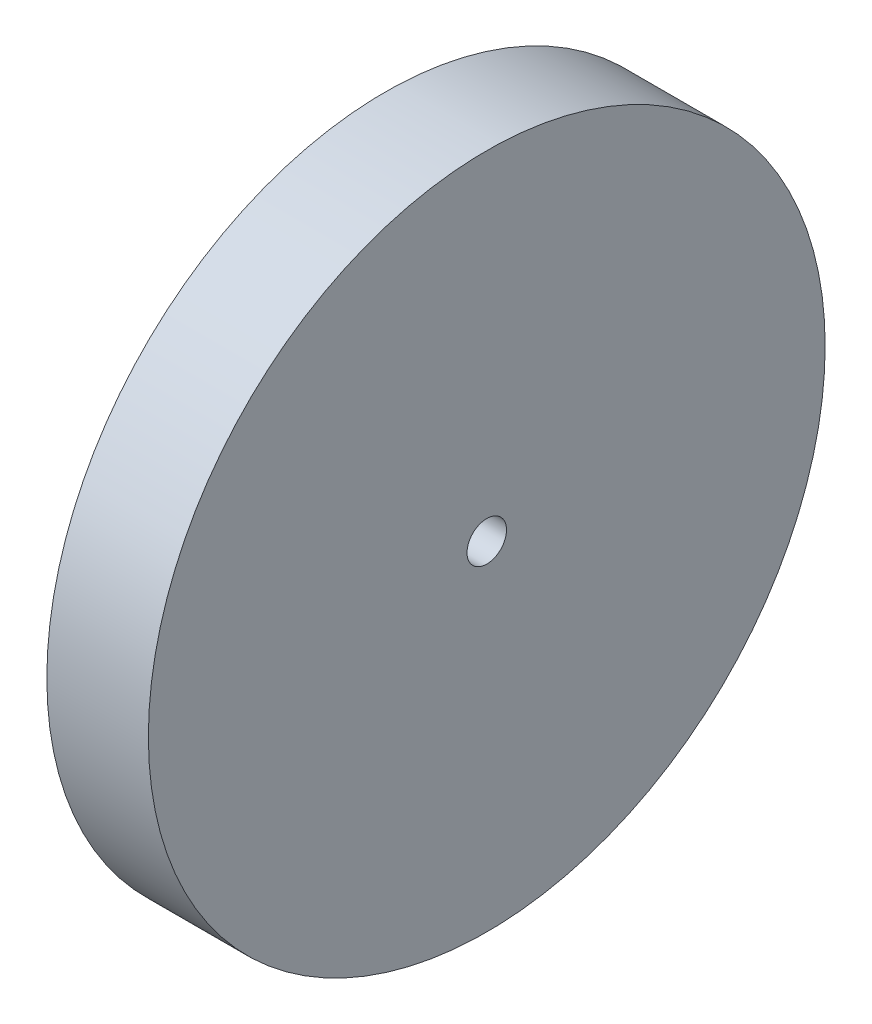
SolidWorks part; units mm, degrees
ref_plane "Front Plane" through (0, 0, 0) normal (0, 0, 1) x (1, 0, 0)
ref_plane "Top Plane" through (0, 0, 0) normal (0, 1, 0) x (1, 0, 0)
ref_plane "Right Plane" through (0, 0, 0) normal (1, 0, 0) x (0, 0, -1)
sketch "Sketch1" plane through (0, 0, 0) normal (1, 0, 0) x (0, 0, -1)
  circle A0 centre (0, 0) radius 50
  circle A1 centre (0, 0) radius 2.9167
  dimension "D1" = 100
extrude "Boss-Extrude1" add sketch "Sketch1" along normal blind 15
